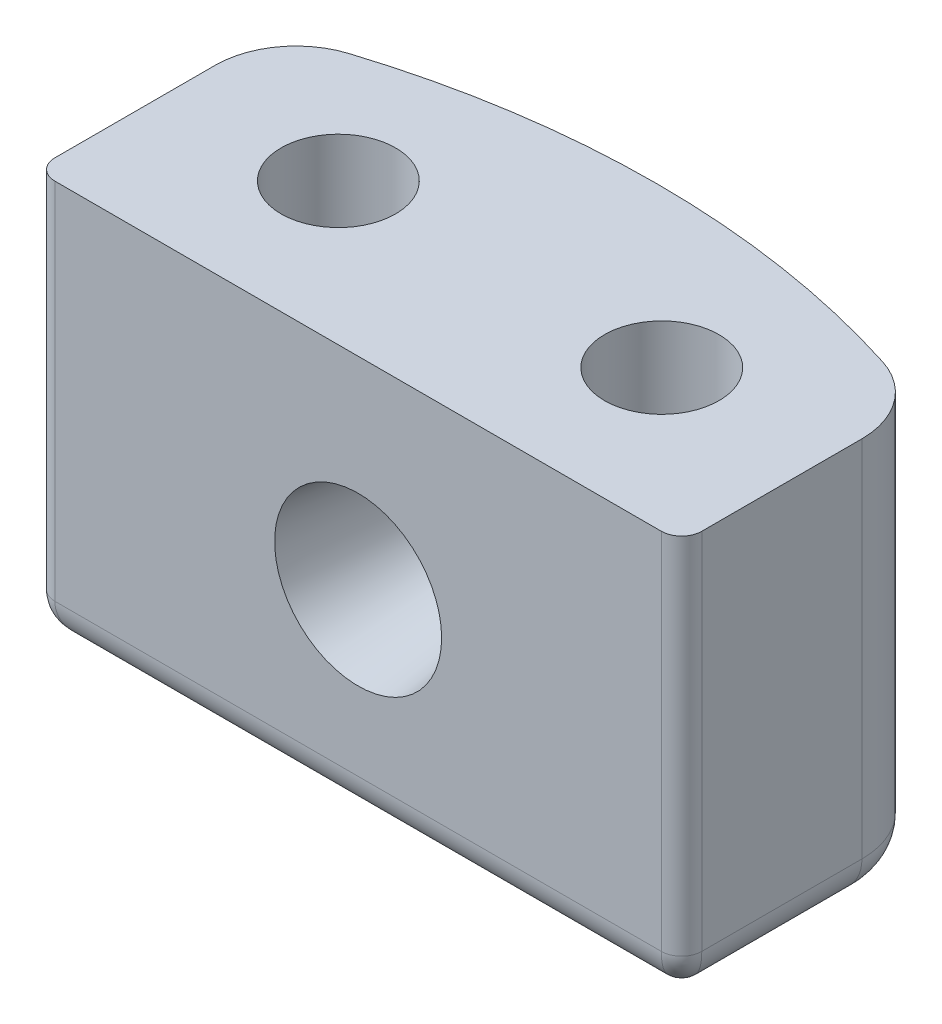
SolidWorks part; units mm, degrees
material "ABS"
ref_plane "Front" through (0, 0, 0) normal (0, 0, 1) x (1, 0, 0)
ref_plane "Top" through (0, 0, 0) normal (0, 1, 0) x (1, 0, 0)
ref_plane "Right" through (0, 0, 0) normal (1, 0, 0) x (0, 0, -1)
sketch "Sketch1" plane through (0, 0, 0) normal (0, 1, 0) x (1, 0, 0)
  line L0 (0, 0) -> (0, 11.7327) construction
  line L1 (-12.7, 0) -> (12.7, 0)
  line L2 (-12.7, 0) -> (-12.7, 9.3229)
  line L3 (12.7, 0) -> (12.7, 9.3229)
  line L4 (-6.35, 5.5731) -> (6.35, 5.5731) construction
  line L5 (-6.35, 5.5731) -> (0, -22.9383) construction
  line L6 (-6.35, 5.5731) -> (-6.35, 0) construction
  line L7 (-6.35, 5.5731) -> (-6.35, 11.1462) construction
  line L8 (-6.35, 2.7866) -> (0, 2.7866) construction
  line L9 (-6.35, 2.7866) -> (-12.7, 2.7866) construction
  arc A0 (-12.7, 9.3229) -> (12.7, 9.3229) centre (0, -22.9383) cw
  point P0 (0, 0)
  point P10 (0, 5.5731)
  dimension "D2" = 69.342
  dimension "D4" = 29.21
  dimension "D1" = 12.7
extrude "Boss-Extrude1" add sketch "Sketch1" along normal blind 15.875
hole_wizard "#8 Clearance Hole1" positions "Sketch2" profile "Sketch4" hole size "#8" standard "ANSI Inch" end condition up to next
sketch "Sketch2" plane through (0, 15.875, 0) normal (0, 1, 0) x (1, 0, 0)
  point P76 (6.35, 5.5731)
  point P78 (-6.35, 5.5731)
sketch "Sketch4" plane through (6.35, 15.875, -5.5731) normal (1, 0, 0) x (0, 0, 1)
  line L0 (0, 0) -> (0, 15.875)
  line L1 (0, 15.875) -> (2.2479, 15.875)
  line L2 (2.2479, 15.875) -> (2.2479, 0)
  line L5 (2.2479, 0) -> (0, 0)
  line L11 (0, -6.35) -> (0, 107.95) construction
  dimension "Thru Hole Dia." = 4.4958
  dimension "Thru Hole Depth" = 15.875
hole_wizard "#5 (0.2055) Diameter Hole1" positions "Sketch5" profile "Sketch6" hole size "#5" standard "ANSI Inch" end condition through all
sketch "Sketch5" plane through (0, 0, 0) normal (0, 0, 1) x (1, 0, 0)
  line L10 (0, 0) -> (0, 15.875) construction
  line L11 (-12.7, 0) -> (12.7, 0) construction
  line L12 (-12.7, 15.875) -> (12.7, 15.875) construction
  point P0 (0, 7.9375)
sketch "Sketch6" plane through (0, 7.9375, 0) normal (1, 0, 0) x (0, -1, 0)
  line L0 (0, 0) -> (0, 11.7327)
  line L1 (0, 11.7327) -> (2.6098, 11.7327)
  line L2 (2.6098, 11.7327) -> (2.6098, 0)
  line L5 (2.6098, 0) -> (0, 0)
  line L11 (0, -6.35) -> (0, 107.95) construction
  dimension "Thru Hole Dia." = 5.2197
  dimension "Thru Hole Depth" = 11.7327
chamfer "Chamfer1" distance 4.7625 angle 8 1 edges at (2.6098, 7.9375, 0) first distance on face at (2.6098, 7.9375, 0)
fillet "Fillet2" radius 3.175 2 edges at (12.7, 7.9375, -9.3229) (-12.7, 7.9375, -9.3229)
fillet "Fillet3" radius 0.7937 2 edges at (-12.7, 7.9375, 0) (12.7, 7.9375, 0)
hole_wizard "CBORE for #8 Button Head Cap Screw1" positions "Sketch7" profile "Sketch9" counterbore size "#8" standard "ANSI Inch" end condition through all
sketch "Sketch7" plane through (0, 0, 0) normal (0, -1, 0) x (-1, 0, 0)
  point P0 (6.35, 5.5731)
  point P3 (-6.35, 5.5731)
sketch "Sketch9" plane through (-6.35, 0, -5.5731) normal (1, 0, 0) x (0, 0, -1)
  line L0 (0, 0) -> (0, 15.875)
  line L1 (0, 15.875) -> (2.2479, 15.875)
  line L3 (2.2479, 15.875) -> (2.2479, 4.1656)
  line L4 (2.2479, 4.1656) -> (4.191, 4.1656)
  line L5 (4.191, 4.1656) -> (4.191, 0)
  line L7 (4.191, 0) -> (0, 0)
  line L11 (0, -6.35) -> (0, 107.95) construction
  dimension "Thru Hole Dia." = 4.4958
  dimension "Thru Hole Depth" = 15.875
  dimension "C'Bore Dia." = 8.382
  dimension "C'Bore Depth" = 4.1656
fillet "Fillet4" radius 1.5875 8 edges at (0, 0, -11.7327) (-12.4675, 0, -0.2325) (-12.7, 0, -3.9383) (-12.0871, 0, -8.958) (12.0871, 0, -8.958) (12.7, 0, -3.9383) (12.4675, 0, -0.2325) (0, 0, 0)
equation "\"D2@Sketch1\"=2.75-0.02"
